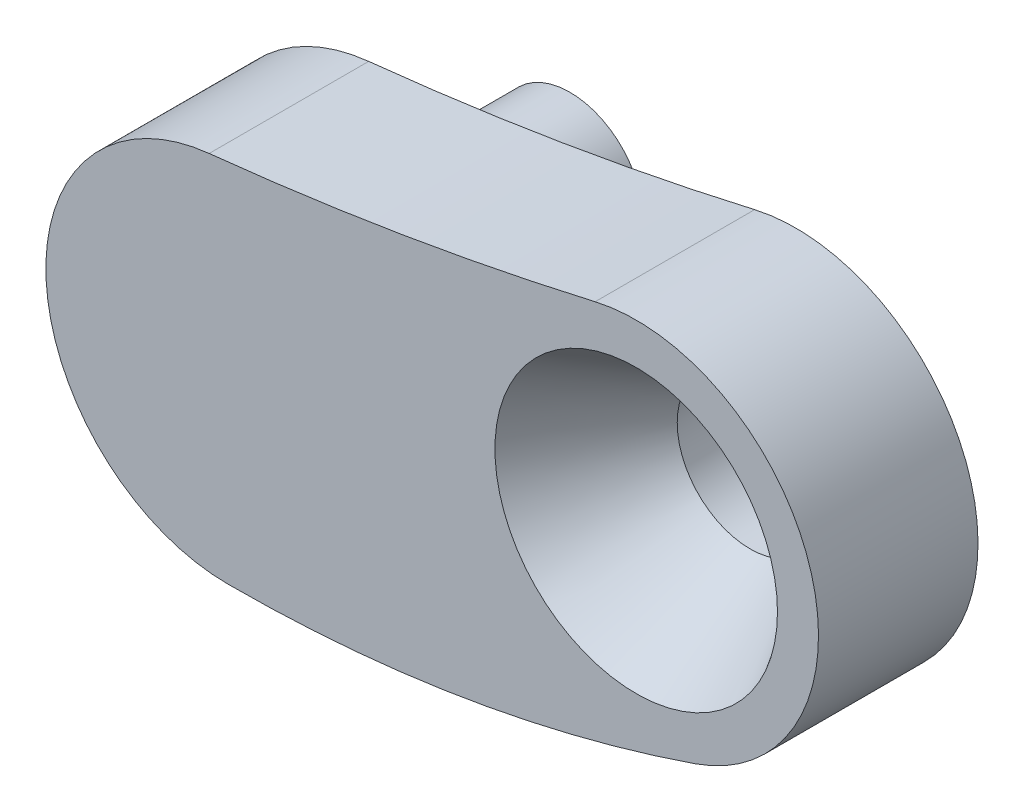
SolidWorks part; units mm, degrees
material "6061 合金"
ref_plane "前视基准面" through (0, 0, 0) normal (0, 0, 1) x (1, 0, 0)
ref_plane "上视基准面" through (0, 0, 0) normal (0, 1, 0) x (1, 0, 0)
ref_plane "右视基准面" through (0, 0, 0) normal (1, 0, 0) x (0, 0, -1)
other "Configuration Table"
sketch "草图1" plane through (0, 0, 0) normal (0, 0, 1) x (1, 0, 0)
  line L1 (0, 0) -> (12.6305, -24.4279) construction
  line L2 (0, 0) -> (8.9531, -26.0018) construction
  line L3 (0, 0) -> (0, -27.5) construction
  line L4 (-3.9575, -26.9182) -> (0, 0) construction
  circle A0 centre (0, 0) radius 27.5 construction
  arc A1 (-0.417, -23.5218) -> (0, -31.5) centre (0, -27.5) ccw
  circle A2 centre (8.9531, -26.0018) radius 1.6
  arc A3 (10.2554, -29.7838) -> (8.0522, -22.1045) centre (8.9531, -26.0018) ccw
  arc A4 (-0.417, -23.5218) -> (8.0522, -22.1045) centre (-7.714, 46.0968) ccw
  circle A6 centre (0, -27.5) radius 1.6 construction
  arc A9 (0, -31.5) -> (10.2554, -29.7838) centre (0, 0) ccw
  point P7 (9.9067, -29.8812)
  dimension "D1" = 55
  dimension "D2" = 8
  dimension "D5" = 3.2
  dimension "D7" = 70
  dimension "D9" = 3.2
  dimension "D10" = 19
extrude "凸台-拉伸1" add sketch "草图1" along normal blind 4 contours A1 A9 A3 A4 A2 region at (4.1865, -26.9162, 0)
sketch "草图2" plane through (0, 0, 0) normal (0, 0, 1) x (1, 0, 0)
  circle A0 centre (0, -27.5) radius 1.6
  point P2 (0, -27.5)
  dimension "D1" = 3.2
extrude "凸台-拉伸2" add sketch "草图2" against normal blind 4
ref_axis "基准轴1" through (8.9531, -26.0018, 4) along (0, 0, -1)
ref_plane "基准面1" through (0, -26.0018, 0) normal (0, 1, 0) x (1, 0, 0)
sketch "草图3" plane through (0, -26.0018, 0) normal (0, 1, 0) x (1, 0, 0)
  line L0 (8.9531, -2.5) -> (8.9531, -3.5) construction
  line L1 (8.9531, -4) -> (8.9531, 0) construction
  line L2 (12.9531, 0) -> (8.0522, 0) construction
  line L7 (8.9531, 0) -> (8.9531, -3.5) construction
  line L8 (8.0522, 0) -> (-0.417, 0) construction
  line L9 (8.9531, -3.5) -> (5.8531, -3.5)
  line L11 (5.8531, -3.5) -> (7.3531, -1)
  line L12 (7.3531, -1) -> (8.9531, -1)
  line L13 (8.9531, -1) -> (8.9531, -3.5)
  dimension "D1" = 6.2
  dimension "D2" = 2.5
  dimension "D3" = 3.2
  dimension "D4" = 1
revolve "切除-旋转1" cut sketch "草图3" angle 360 about L13
sketch "草图5" plane through (0, 0, 4) normal (0, 0, 1) x (1, 0, 0)
  arc A4 (-0.417, -23.5218) -> (0, -31.5) centre (0, -27.5) ccw
  arc A5 (0, -31.5) -> (10.2554, -29.7838) centre (0, 0) ccw
  arc A6 (10.2554, -29.7838) -> (8.0522, -22.1045) centre (8.9531, -26.0018) ccw
  arc A7 (-0.417, -23.5218) -> (8.0522, -22.1045) centre (-7.714, 46.0968) ccw
  arc A8 (-0.417, -23.5218) -> (0, -31.5) centre (0, -27.5) ccw
  arc A9 (0, -31.5) -> (10.2554, -29.7838) centre (0, 0) ccw
  arc A10 (10.2554, -29.7838) -> (8.0522, -22.1045) centre (8.9531, -26.0018) ccw
  arc A11 (-0.417, -23.5218) -> (8.0522, -22.1045) centre (-7.714, 46.0968) ccw
  dimension "D1" = 0
extrude "切除-拉伸1" cut sketch "草图5" against normal blind 0.5
